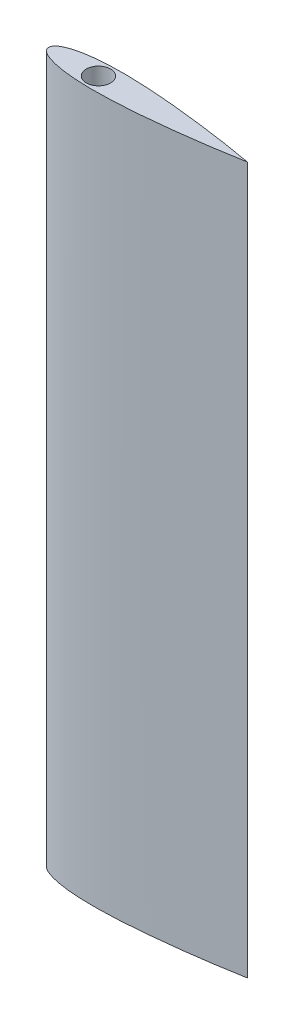
SolidWorks part; units mm, degrees
material "Polyurethane Foam Rigid"
ref_plane "Front Plane" through (0, 0, 0) normal (0, 0, 1) x (1, 0, 0)
ref_plane "Top Plane" through (0, 0, 0) normal (0, 1, 0) x (1, 0, 0)
ref_plane "Right Plane" through (0, 0, 0) normal (1, 0, 0) x (0, 0, -1)
ref_plane "Plane4" through (0, 31.75, 0) normal (0, 1, 0) x (1, 0, 0)
sketch "rootSketch" plane through (0, 31.75, 0) normal (0, 1, 0) x (1, 0, 0)
  line L0 (0, 0) -> (1500, 0) construction
  line L2 (13, -3.9) -> (13, 3.9) construction
  line L3 (0, 0) -> (52, 0) construction
  spline S0 degree 4 poles (0, 0) (0, 0.0566) (0.0054, 0.148) (0.0261, 0.2802) (0.0778, 0.4522) (0.1471, 0.6119) (0.2485, 0.786) (0.3924, 0.9775) (0.5992, 1.1954) (0.9058, 1.4518) (1.3705, 1.7579) (2.0783, 2.1191) (3.1757, 2.542) (4.8233, 2.9987) (7.2754, 3.453) (10.4387, 3.7805) (14.1293, 3.9293) (18.1436, 3.8963) (22.1517, 3.7223) (25.6562, 3.476) (28.6515, 3.2136) (31.6507, 2.914) (34.1342, 2.6396) (36.6395, 2.3366) (39.5995, 1.9537) (42.1279, 1.6007) (44.5332, 1.2475) (47.1211, 0.8374) (48.9103, 0.5455) (51.4233, 0.1075) (52.8542, -0.154) (54.9428, -0.5501) (55.9597, -0.7584) (56.7861, -0.9233) (56.9961, -0.9696) (57.2092, -1.0126) knots 0 0 0 0 0 0.003841 0.006235 0.009072 0.012193 0.015657 0.019917 0.025339 0.032593 0.042799 0.057705 0.079311 0.112503 0.158973 0.227236 0.2955 0.363764 0.432028 0.500292 0.534424 0.568556 0.63682 0.670952 0.705084 0.773347 0.807479 0.841611 0.875743 0.909875 0.954938 0.977469 0.988734 1 1 1 1 1 construction
  spline S1 degree 4 poles (0, 0) (0, 0.0566) (0.0054, 0.148) (0.0261, 0.2802) (0.0778, 0.4522) (0.1471, 0.6119) (0.2485, 0.786) (0.3924, 0.9775) (0.5992, 1.1954) (0.9058, 1.4518) (1.3705, 1.7579) (2.0783, 2.1191) (3.1757, 2.542) (4.8233, 2.9987) (7.2754, 3.453) (10.4387, 3.7805) (14.1293, 3.9293) (18.1436, 3.8963) (22.1517, 3.7223) (25.6562, 3.476) (28.6515, 3.2136) (31.6507, 2.914) (34.1342, 2.6396) (36.6395, 2.3366) (39.5995, 1.9537) (42.1279, 1.6007) (44.5332, 1.2475) (47.1211, 0.8374) (48.9103, 0.5455) (50.6553, 0.2414) (51.551, 0.0816) (52, 0) knots 0 0 0 0 0 0.003841 0.006235 0.009072 0.012193 0.015657 0.019917 0.025339 0.032593 0.042799 0.057705 0.079311 0.112503 0.158973 0.227236 0.2955 0.363764 0.432028 0.500292 0.534424 0.568556 0.63682 0.670952 0.705084 0.773347 0.807479 0.841611 0.875743 0.909875 0.909875 0.909875 0.909875 0.909875
  spline S2 degree 4 poles (0, 0) (0, -0.0566) (0.0054, -0.148) (0.0261, -0.2802) (0.0778, -0.4522) (0.1471, -0.6119) (0.2485, -0.786) (0.3924, -0.9775) (0.5992, -1.1954) (0.9058, -1.4518) (1.3705, -1.7579) (2.0783, -2.1191) (3.1757, -2.542) (4.8233, -2.9987) (7.2754, -3.453) (10.4387, -3.7805) (14.1293, -3.9293) (18.1436, -3.8963) (22.1517, -3.7223) (25.6562, -3.476) (28.6515, -3.2136) (31.6507, -2.914) (34.1342, -2.6396) (36.6395, -2.3366) (39.5995, -1.9537) (42.1279, -1.6007) (44.5332, -1.2475) (47.1211, -0.8374) (48.9103, -0.5455) (51.4233, -0.1075) (52.8542, 0.154) (54.9428, 0.5501) (55.9597, 0.7584) (56.7861, 0.9233) (56.9961, 0.9696) (57.2092, 1.0126) knots 0 0 0 0 0 0.003841 0.006235 0.009072 0.012193 0.015657 0.019917 0.025339 0.032593 0.042799 0.057705 0.079311 0.112503 0.158973 0.227236 0.2955 0.363764 0.432028 0.500292 0.534424 0.568556 0.63682 0.670952 0.705084 0.773347 0.807479 0.841611 0.875743 0.909875 0.954938 0.977469 0.988734 1 1 1 1 1 construction
  spline S3 degree 4 poles (0, 0) (0, -0.0566) (0.0054, -0.148) (0.0261, -0.2802) (0.0778, -0.4522) (0.1471, -0.6119) (0.2485, -0.786) (0.3924, -0.9775) (0.5992, -1.1954) (0.9058, -1.4518) (1.3705, -1.7579) (2.0783, -2.1191) (3.1757, -2.542) (4.8233, -2.9987) (7.2754, -3.453) (10.4387, -3.7805) (14.1293, -3.9293) (18.1436, -3.8963) (22.1517, -3.7223) (25.6562, -3.476) (28.6515, -3.2136) (31.6507, -2.914) (34.1342, -2.6396) (36.6395, -2.3366) (39.5995, -1.9537) (42.1279, -1.6007) (44.5332, -1.2475) (47.1211, -0.8374) (48.9103, -0.5455) (50.6553, -0.2414) (51.551, -0.0816) (52, 0) knots 0 0 0 0 0 0.003841 0.006235 0.009072 0.012193 0.015657 0.019917 0.025339 0.032593 0.042799 0.057705 0.079311 0.112503 0.158973 0.227236 0.2955 0.363764 0.432028 0.500292 0.534424 0.568556 0.63682 0.670952 0.705084 0.773347 0.807479 0.841611 0.875743 0.909875 0.909875 0.909875 0.909875 0.909875
  point P10 (13, 0)
  dimension "incidenceAngle" = 0
  dimension "rootChord" = 52
  dimension "rootQuarterChord" = 13
  dimension "rootMaxThickness" = 7.8
ref_plane "Plane1" through (0, 216.6684, 0) normal (0, 1, 0) x (1, 0, 0)
sketch "tipSketch" plane through (0, 216.6684, 0) normal (0, 1, 0) x (1, 0, 0)
  line L0 (216.8234, 0) -> (518.1352, 0) construction
  line L3 (0, 0) -> (52, 0) construction
  line L4 (13, -3.9) -> (13, 3.9) construction
  spline S0 degree 4 poles (0, 0) (0, 0.0566) (0.0054, 0.148) (0.0261, 0.2802) (0.0778, 0.4522) (0.1471, 0.6119) (0.2485, 0.786) (0.3924, 0.9775) (0.5992, 1.1954) (0.9058, 1.4518) (1.3705, 1.7579) (2.0783, 2.1191) (3.1757, 2.542) (4.8233, 2.9987) (7.2754, 3.453) (10.4387, 3.7805) (14.1293, 3.9293) (18.1436, 3.8963) (22.1517, 3.7223) (25.6562, 3.476) (28.6515, 3.2136) (31.6507, 2.914) (34.1342, 2.6396) (36.6395, 2.3366) (39.5995, 1.9537) (42.1279, 1.6007) (44.5332, 1.2475) (47.1211, 0.8374) (48.9103, 0.5455) (51.4233, 0.1075) (52.8542, -0.154) (54.9428, -0.5501) (55.9597, -0.7584) (56.7861, -0.9233) (56.9961, -0.9696) (57.2092, -1.0126) knots 0 0 0 0 0 0.003841 0.006235 0.009072 0.012193 0.015657 0.019917 0.025339 0.032593 0.042799 0.057705 0.079311 0.112503 0.158973 0.227236 0.2955 0.363764 0.432028 0.500292 0.534424 0.568556 0.63682 0.670952 0.705084 0.773347 0.807479 0.841611 0.875743 0.909875 0.954938 0.977469 0.988734 1 1 1 1 1 construction
  spline S1 degree 4 poles (0, 0) (0, 0.0566) (0.0054, 0.148) (0.0261, 0.2802) (0.0778, 0.4522) (0.1471, 0.6119) (0.2485, 0.786) (0.3924, 0.9775) (0.5992, 1.1954) (0.9058, 1.4518) (1.3705, 1.7579) (2.0783, 2.1191) (3.1757, 2.542) (4.8233, 2.9987) (7.2754, 3.453) (10.4387, 3.7805) (14.1293, 3.9293) (18.1436, 3.8963) (22.1517, 3.7223) (25.6562, 3.476) (28.6515, 3.2136) (31.6507, 2.914) (34.1342, 2.6396) (36.6395, 2.3366) (39.5995, 1.9537) (42.1279, 1.6007) (44.5332, 1.2475) (47.1211, 0.8374) (48.9103, 0.5455) (50.6553, 0.2414) (51.551, 0.0816) (52, 0) knots 0 0 0 0 0 0.003841 0.006235 0.009072 0.012193 0.015657 0.019917 0.025339 0.032593 0.042799 0.057705 0.079311 0.112503 0.158973 0.227236 0.2955 0.363764 0.432028 0.500292 0.534424 0.568556 0.63682 0.670952 0.705084 0.773347 0.807479 0.841611 0.875743 0.909875 0.909875 0.909875 0.909875 0.909875
  spline S2 degree 4 poles (0, 0) (0, -0.0566) (0.0054, -0.148) (0.0261, -0.2802) (0.0778, -0.4522) (0.1471, -0.6119) (0.2485, -0.786) (0.3924, -0.9775) (0.5992, -1.1954) (0.9058, -1.4518) (1.3705, -1.7579) (2.0783, -2.1191) (3.1757, -2.542) (4.8233, -2.9987) (7.2754, -3.453) (10.4387, -3.7805) (14.1293, -3.9293) (18.1436, -3.8963) (22.1517, -3.7223) (25.6562, -3.476) (28.6515, -3.2136) (31.6507, -2.914) (34.1342, -2.6396) (36.6395, -2.3366) (39.5995, -1.9537) (42.1279, -1.6007) (44.5332, -1.2475) (47.1211, -0.8374) (48.9103, -0.5455) (51.4233, -0.1075) (52.8542, 0.154) (54.9428, 0.5501) (55.9597, 0.7584) (56.7861, 0.9233) (56.9961, 0.9696) (57.2092, 1.0126) knots 0 0 0 0 0 0.003841 0.006235 0.009072 0.012193 0.015657 0.019917 0.025339 0.032593 0.042799 0.057705 0.079311 0.112503 0.158973 0.227236 0.2955 0.363764 0.432028 0.500292 0.534424 0.568556 0.63682 0.670952 0.705084 0.773347 0.807479 0.841611 0.875743 0.909875 0.954938 0.977469 0.988734 1 1 1 1 1 construction
  spline S3 degree 4 poles (0, 0) (0, -0.0566) (0.0054, -0.148) (0.0261, -0.2802) (0.0778, -0.4522) (0.1471, -0.6119) (0.2485, -0.786) (0.3924, -0.9775) (0.5992, -1.1954) (0.9058, -1.4518) (1.3705, -1.7579) (2.0783, -2.1191) (3.1757, -2.542) (4.8233, -2.9987) (7.2754, -3.453) (10.4387, -3.7805) (14.1293, -3.9293) (18.1436, -3.8963) (22.1517, -3.7223) (25.6562, -3.476) (28.6515, -3.2136) (31.6507, -2.914) (34.1342, -2.6396) (36.6395, -2.3366) (39.5995, -1.9537) (42.1279, -1.6007) (44.5332, -1.2475) (47.1211, -0.8374) (48.9103, -0.5455) (50.6553, -0.2414) (51.551, -0.0816) (52, 0) knots 0 0 0 0 0 0.003841 0.006235 0.009072 0.012193 0.015657 0.019917 0.025339 0.032593 0.042799 0.057705 0.079311 0.112503 0.158973 0.227236 0.2955 0.363764 0.432028 0.500292 0.534424 0.568556 0.63682 0.670952 0.705084 0.773347 0.807479 0.841611 0.875743 0.909875 0.909875 0.909875 0.909875 0.909875
  point P10 (13, 0)
  dimension "incidenceAngle" = 0
  dimension "tipChord" = 52
  dimension "tipQuarterChord" = 13
  dimension "tipMaxThickness" = 7.8
  dimension "sweepOffset" = 0
loft "Loft1" add profiles "rootSketch", "tipSketch" connector at (52, 31.75, 0) connector at (52, 216.6684, 0)
ref_plane "Plane2" through (52, 0, 0) normal (1, 0, 0) x (0, 0, -1)
sketch "rudderSketch" plane through (0, 0, 0) normal (0, 0, 1) x (1, 0, 0)
  line L0 (52, 31.75) -> (52, 85.9171) construction
  line L1 (52, 31.75) -> (52, 194.2513) construction
  line L2 (52, 85.9171) -> (78, 85.9171) construction
  line L3 (52, 194.2513) -> (78, 194.2513) construction
  line L4 (78, 194.2513) -> (78, 85.9171)
  line L5 (78, 194.2513) -> (130, 194.2513)
  line L6 (78, 85.9171) -> (130, 85.9171)
  line L7 (130, 85.9171) -> (130, 194.2513)
  line L8 (129.5667, 86.3504) -> (129.5667, 193.818)
  line L9 (78.4333, 193.818) -> (129.5667, 193.818)
  line L10 (78.4333, 193.818) -> (78.4333, 86.3504)
  line L11 (78.4333, 86.3504) -> (129.5667, 86.3504)
  dimension "rudderStartyLoc" = 54.1671
  dimension "rudderEndyLoc" = 162.5013
  dimension "rudderStartxLoc" = 26
  dimension "rudderEndeLoc" = 26
  dimension "D1" = 52
  dimension "D2" = 52
extrude "Cut-Extrude1" [suppressed] cut sketch "rudderSketch" against normal blind 200 and the other way blind 200
sketch "Sketch1" plane through (0, 31.75, 0) normal (0, 1, 0) x (1, 0, 0)
  line L0 (0, 0) -> (52, 0) construction
  line L2 (52, 3.9004) -> (52, -3.9004) construction
  line L4 (0, -3.9004) -> (0, 3.9004) construction
  line L6 (13, 3.8615) -> (13, -3.8615) construction
  circle A0 centre (13, 0) radius 3.175
  circle A1 centre (13, 0) radius 1.9304 construction
  spline S0 degree 3 poles (52, 0) (49.8075, 0.3984) (45.4111, 1.1322) (39.8961, 1.9224) (35.4744, 2.4815) (32.1534, 2.8618) (28.8277, 3.1988) (25.4973, 3.4855) (22.7181, 3.674) (20.4925, 3.7875) (18.8224, 3.8515) (17.1515, 3.8919) (15.4802, 3.9055) (13.8089, 3.8885) (12.1383, 3.836) (10.4694, 3.7424) (9.0816, 3.6237) (7.9743, 3.4989) (7.1459, 3.3887) (6.3202, 3.2597) (5.4981, 3.1092) (4.681, 2.9337) (3.8708, 2.7284) (3.0706, 2.4866) (2.2858, 2.1982) (1.6528, 1.9059) (1.1703, 1.6264) (0.8267, 1.3881) (0.5106, 1.1133) (0.2403, 0.7926) (0.0469, 0.4177) (0, 0.1393) (0, 0) knots 0 0 0 0 0.062499 0.124998 0.156248 0.187497 0.218747 0.249996 0.281246 0.296871 0.312496 0.32812 0.343745 0.35937 0.374995 0.39062 0.406244 0.414057 0.421869 0.429681 0.437494 0.445306 0.453119 0.460931 0.468743 0.476556 0.480462 0.484368 0.488274 0.492181 0.496087 0.499993 0.499993 0.499993 0.499993 construction
  spline S1 degree 3 poles (0, 0) (0, -0.1393) (0.0469, -0.4177) (0.2403, -0.7926) (0.5106, -1.1133) (0.8267, -1.3881) (1.1703, -1.6264) (1.6528, -1.9059) (2.2858, -2.1982) (3.0706, -2.4866) (3.8708, -2.7284) (4.681, -2.9337) (5.4981, -3.1092) (6.3202, -3.2597) (7.1459, -3.3887) (7.9743, -3.4989) (9.0816, -3.6237) (10.4694, -3.7424) (12.1383, -3.836) (13.8089, -3.8885) (15.4802, -3.9055) (17.1515, -3.8919) (18.8224, -3.8515) (20.4925, -3.7875) (22.7181, -3.674) (25.4973, -3.4855) (28.8277, -3.1988) (32.1534, -2.8618) (35.4744, -2.4815) (39.8961, -1.9224) (45.4111, -1.1322) (49.8075, -0.3984) (52, 0) knots 0.499993 0.499993 0.499993 0.499993 0.503899 0.507806 0.511712 0.515618 0.519525 0.523431 0.531243 0.539056 0.546869 0.554681 0.562494 0.570306 0.578119 0.585932 0.593744 0.60937 0.624995 0.64062 0.656245 0.67187 0.687496 0.703121 0.718746 0.749996 0.781247 0.812497 0.843748 0.874998 0.937499 1 1 1 1 construction
  dimension "D1" = 6.35
  dimension "D2" = 3.8608
  dimension "D3" = 52
  dimension "D4" = 13
extrude "Cut-Extrude2" cut sketch "Sketch1<2>" along normal through all
sketch "Sketch1<2>" plane through (0, 31.75, 0) normal (0, 1, 0) x (1, 0, 0) same geometry as "Sketch1"
extrude "Boss-Extrude1" [suppressed] add sketch "Sketch1" along normal up to surface and the other way blind 17.145 separate body up to face at (13, 216.6684, -3.175)
sketch "Sketch3" plane through (0, 31.75, 0) normal (0, 1, 0) x (1, 0, 0)
  circle A0 centre (13, 0) radius 3.9688
  circle A1 centre (13, 0) radius 3.175 construction
  dimension "D1" = 7.9375
extrude "Boss-Extrude2" [suppressed] add sketch "Sketch3" against normal blind 3.81
ref_axis "Axis1" [suppressed] through (15.5748, 28.575, 0) along (0, -1, 0)
ref_plane "Plane3" [suppressed] through (15.5748, 0, 0) normal (-1, 0, 0) x (0, -1, 0)
sketch "Sketch2" [suppressed] plane through (15.5748, 0, 0) normal (1, 0, 0) x (0, 0, -1)
  line L0 (0, 14.605) -> (0, 27.94) construction
  line L1 (6.35, 23.9712) -> (3.175, 23.9712)
  line L2 (6.35, 23.9712) -> (6.35, 27.94)
  line L3 (6.35, 27.94) -> (3.175, 27.94)
  line L4 (19.05, 23.9713) -> (19.05, 27.94) construction
  line L5 (-3.175, 14.605) -> (3.175, 14.605) construction
  line L7 (-3.175, 27.94) -> (3.175, 27.94) construction
  line L8 (3.175, 15.24) -> (3.175, 19.2087)
  line L9 (6.35, 15.24) -> (3.175, 15.24)
  line L10 (6.35, 15.24) -> (6.35, 19.2087)
  line L11 (6.35, 19.2087) -> (3.175, 19.2087)
  line L12 (19.05, 15.24) -> (19.05, 19.2088) construction
  line L13 (3.175, 23.9712) -> (3.175, 27.94)
  line L14 (-3.175, 15.24) -> (-3.175, 19.2087) construction
  line L15 (-3.175, 23.9712) -> (-3.175, 27.94) construction
  line L16 (3.175, 14.605) -> (3.175, 27.94) construction
  line L17 (-3.175, 15.24) -> (19.05, 15.24) construction
  line L18 (-3.175, 19.2087) -> (19.05, 19.2088) construction
  line L19 (-3.175, 23.9712) -> (19.05, 23.9713) construction
  line L20 (-3.175, 27.94) -> (19.05, 27.94) construction
  line L21 (-3.9688, 27.94) -> (3.9687, 27.94) construction
  dimension "D1" = 3.9688
  dimension "D2" = 12.7
  dimension "D3" = 12.7
  dimension "D4" = 6.35
revolve "Revolve1" [suppressed] add sketch "Sketch2" angle 360 about L0
sketch "Sketch4" [suppressed] plane through (0, 14.605, 0) normal (0, -1, 0) x (-1, 0, 0)
  circle A0 centre (-15.5748, 0) radius 3.0226
  circle A1 centre (-15.5748, 0) radius 3.175 construction
  dimension "D1" = 6.0452
extrude "Cut-Extrude3" [suppressed] cut sketch "Sketch4" along normal blind 0.381 from offset 1.27 flip side to cut offset against normal yes
sketch "Sketch5" [suppressed] plane through (0, 27.94, 0) normal (0, -1, 0) x (1, 0, 0)
  line L1 (13.1936, 3.175) -> (17.9561, 3.175)
  line L3 (13.1936, -3.175) -> (17.9561, -3.175)
  arc A0 (17.9561, 3.175) -> (13.1936, 3.175) centre (15.5748, 0) ccw
  circle A1 centre (15.5748, 0) radius 3.9688 construction
  circle A2 centre (15.5748, 0) radius 3.175 construction
  arc A3 (13.1936, -3.175) -> (17.9561, -3.175) centre (15.5748, 0) ccw
extrude "Cut-Extrude6" [suppressed] cut sketch "Sketch5" against normal up to surface (3.81 mm away) up to face at (13, 31.75, 3.175)
sketch "Sketch6" plane through (0, 0, 0) normal (0, 0, 1) x (1, 0, 0)
  line L0 (52, 31.75) -> (52, 216.6684) construction
  line L1 (52, 216.6684) -> (0, 216.6684)
  line L2 (52, 216.6684) -> (52, 31.75)
  line L3 (52, 31.75) -> (0, 31.75)
  line L4 (0, 216.6684) -> (0, 31.75)
  line L5 (0, 31.75) -> (0, 216.6684) construction
  line L6 (52, 216.6684) -> (0, 216.6684) construction
  line L9 (0, 31.75) -> (52, 31.75) construction
equation "\"rootChord@rootSketch\"=(\"rootChord\"+\"rootChord\")/2"
equation "\"incidenceAngle@rootSketch\"=(\"incidentAngle\"+\"incidentAngle\")/2"
equation "\"rootQuarterChord@rootSketch\" = \"rootChord@rootSketch\" / 4"
equation "\"rootMaxThickness@rootSketch\" = \"rootChord\" * \"NACAairfoil\" / 100"
equation "\"halfSpan@Plane1\"= \"rootChord@rootSketch\" * ( 1 + \"taperRatio\" ) / 2 * \"aspectRatio\""
equation "\"incidenceAngle@tipSketch\" = \"incidenceAngle@rootSketch\""
equation "\"tipChord@tipSketch\"= \"rootChord@rootSketch\" * \"taperRatio\""
equation "\"tipQuarterChord@tipSketch\"=\"tipChord@tipSketch\"/4"
equation "\"tipMaxThickness@tipSketch\"=\"tipChord@tipSketch\"*\"NACAairfoil\"/100"
equation "\"rootChord@Plane2\"=\"rootChord@rootSketch\""
equation "\"rudderCenter\"= 0.5'Center of the rudder as a percentage of half span"
equation "\"rudderWidth\"= 0.5'Width of the rudder as a percentage of half span"
equation "\"rudderStartyLoc@rudderSketch\"=\"halfSpan@Plane1\" *  ( \"rudderCenter\" - \"rudderWidth\" / 2 )"
equation "\"rudderEndyLoc@rudderSketch\"=\"halfSpan@Plane1\" *  ( \"rudderCenter\" + \"rudderWidth\" / 2 )"
equation "\"rudderStartxLoc@rudderSketch\"=\"rudderStartyLoc@rudderSketch\"*tan ( \"sweepAngle\" ) + 0.5*(\"rootChord@rootSketch\" + \"rudderStartyLoc@rudderSketch\"*(((\"tipChord@tipSketch\"-\"rootChord@rootSketch\")/\"halfSpan@Plane1\")))"
equation "\"rudderEndeLoc@rudderSketch\"=\"rudderStartyLoc@rudderSketch\"*tan ( \"sweepAngle\" ) + 0.5*(\"rootChord@rootSketch\" + \"rudderStartyLoc@rudderSketch\"*(((\"tipChord@tipSketch\"-\"rootChord@rootSketch\")/\"halfSpan@Plane1\")))"
equation "\"D1@rudderSketch\"=1*\"rootChord@rootSketch\""
equation "\"D2@rudderSketch\"=1*\"rootChord@rootSketch\""
equation "\"D3@rudderSketch\"=\"halfSpan@Plane1\"/500"
equation "\"sweepOffset@tipSketch\" = \"halfSpan@Plane1\" * tan ( \"sweepAngle\" ) "
equation "\"D2@tipSketch\"=\"tipChord@tipSketch\"*tan(\"incidentAngle\")"
equation "\"rootChord\"= 0.052"
equation "\"NACAairfoil\"= 0015"
equation "\"incidentAngle\"= 0"
equation "\"aspectRatio\"= 4.1667"
equation "\"taperRatio\"= 1"
equation "\"sweepAngle\"= 0"
equation "\"D4@Sketch1\"=0.25*\"D3@Sketch1\""
